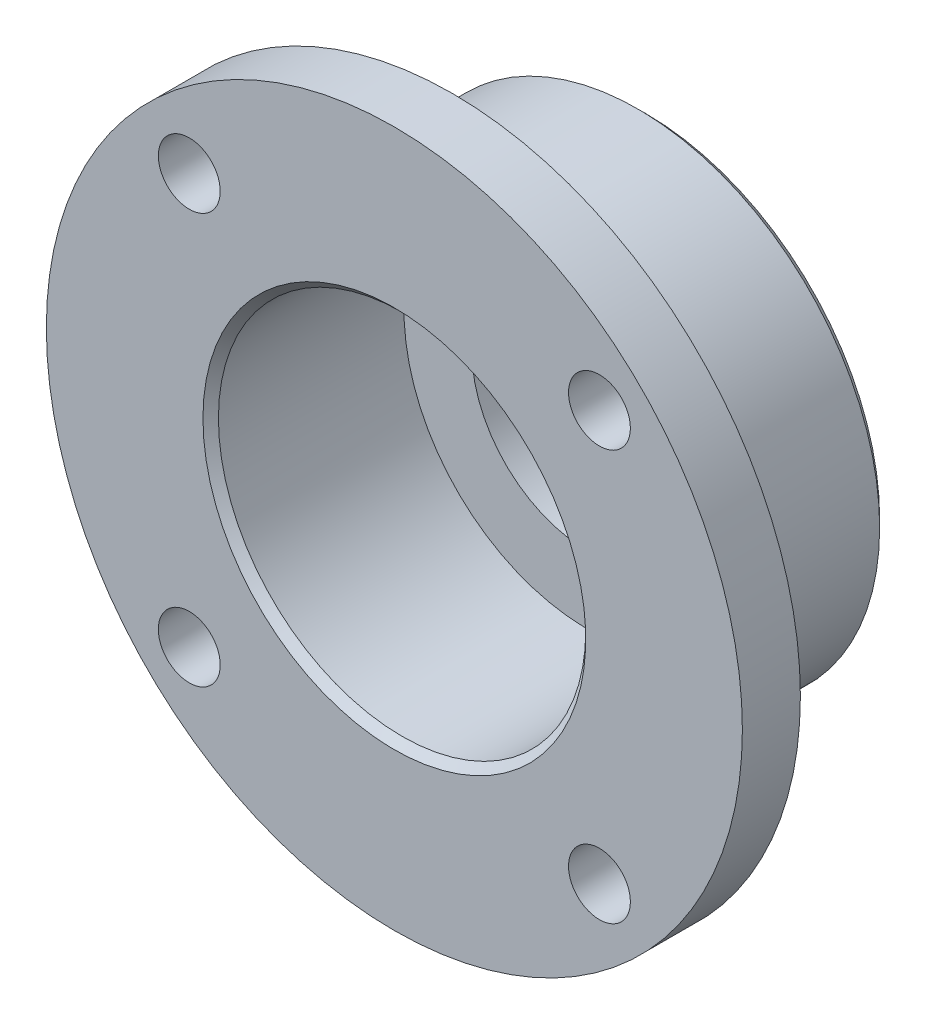
SolidWorks part; units mm, degrees
material "2024 Сплав"
ref_plane "Спереди" through (0, 0, 0) normal (0, 0, 1) x (1, 0, 0)
ref_plane "Сверху" through (0, 0, 0) normal (0, 1, 0) x (1, 0, 0)
ref_plane "Справа" through (0, 0, 0) normal (1, 0, 0) x (0, 0, -1)
sketch "Эскиз1" plane through (0, 0, 0) normal (0, 1, 0) x (1, 0, 0)
  line L0 (-18, 0) -> (-18, 3)
  line L1 (-18, 3) -> (-12.5, 3)
  line L2 (-12.5, 3) -> (-12.5, 13)
  line L3 (-12.5, 13) -> (-6, 13)
  line L4 (-6, 13) -> (-6, 10)
  line L6 (-9.5, 10) -> (-9.5, 0)
  line L7 (-9.5, 0) -> (-18, 0)
  line L8 (0, 0) -> (0, 50000) construction
  line L12 (-9.5, 10) -> (-6, 10)
  dimension "D1" = 6
  dimension "D2" = 12.5
  dimension "D3" = 9.5
  dimension "D4" = 3
  dimension "D5" = 3
  dimension "D6" = 18
  dimension "D7" = 13
revolve "Повернуть1" add sketch "Эскиз1" angle 360 about L8
sketch "Эскиз2" plane through (0, 0, 0) normal (0, 0, 1) x (1, 0, 0)
  line L0 (0, 0) -> (18, 0) construction
  circle A2 centre (0, 0) radius 9.5 construction
  circle A3 centre (10.6066, 10.6066) radius 1.6
  circle A4 centre (0, 0) radius 18 construction
  dimension "D1" = 15
  dimension "D2" = 3.2
  dimension "D3" = 45
extrude "Вырез-Вытянуть1" cut sketch "Эскиз2" against normal up to next
pattern_circular "Круговой массив1" count 4 over 360 about axis through (0, 0, 0) along (0, 0, 1) of "Вырез-Вытянуть1" reverse direction yes
chamfer "Фаска1" distance 0.4 angle 45 2 edges at (12.5, 0, -13) (9.5, 0, 0)
